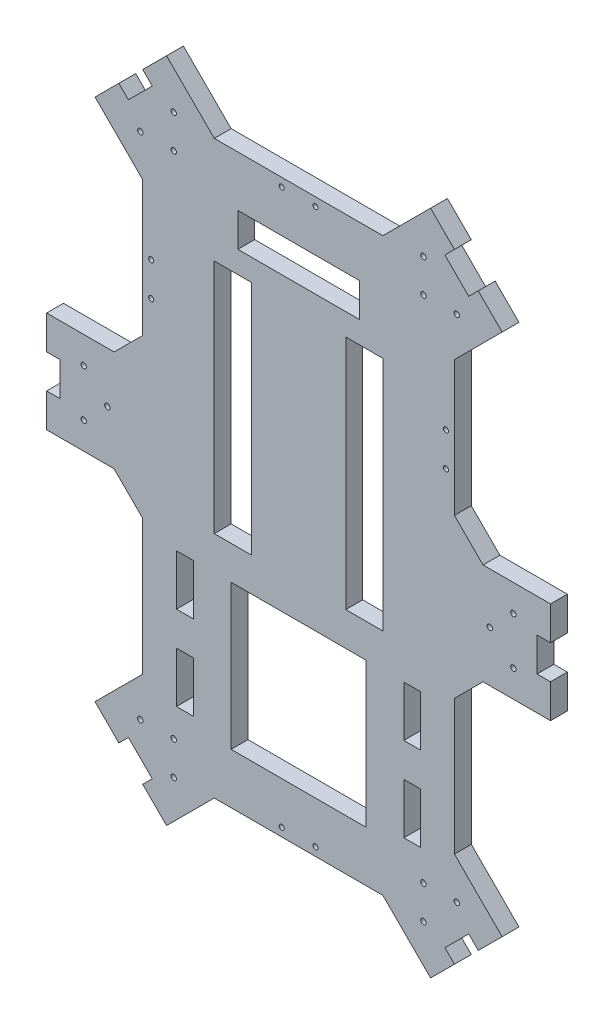
SolidWorks part; units mm, degrees
ref_plane "Płaszczyzna przednia" through (0, 0, 0) normal (0, 0, 1) x (1, 0, 0)
ref_plane "Płaszczyzna górna" through (0, 0, 0) normal (0, 1, 0) x (1, 0, 0)
ref_plane "Płaszczyzna prawa" through (0, 0, 0) normal (1, 0, 0) x (0, 0, -1)
sketch "Szkic1" plane through (0, 0, 0) normal (0, 0, 1) x (1, 0, 0)
  line L0 (0, 0) -> (-50, 0)
  line L1 (-50, 0) -> (-64.1421, 14.1421)
  line L2 (-64.1421, 14.1421) -> (-71.2132, 7.0711)
  line L3 (-71.2132, 7.0711) -> (-68.3848, 4.2426)
  line L4 (-68.3848, 4.2426) -> (-75.4558, -2.8284)
  line L5 (-75.4558, -2.8284) -> (-78.2843, 0)
  line L6 (-78.2843, 0) -> (-85.3553, -7.0711)
  line L7 (-85.3553, -7.0711) -> (-71.2132, -21.2132)
  line L8 (-71.2132, -21.2132) -> (-71.2132, -61.2132)
  line L9 (0, 0) -> (14.1421, 14.1421)
  line L10 (14.1421, 14.1421) -> (21.2132, 7.0711)
  line L11 (21.2132, 7.0711) -> (18.3848, 4.2426)
  line L12 (18.3848, 4.2426) -> (25.4558, -2.8284)
  line L13 (25.4558, -2.8284) -> (28.2843, 0)
  line L14 (28.2843, 0) -> (35.3553, -7.0711)
  line L15 (35.3553, -7.0711) -> (21.2132, -21.2132)
  line L16 (21.2132, -21.2132) -> (21.2132, -61.2132)
  line L17 (-71.2132, -61.2132) -> (-79.6985, -69.6985)
  line L18 (-79.6985, -69.6985) -> (-99.6985, -69.6985)
  line L19 (-99.6985, -69.6985) -> (-99.6985, -79.6985)
  line L20 (-99.6985, -79.6985) -> (-95.6985, -79.6985)
  line L21 (-95.6985, -79.6985) -> (-95.6985, -89.6985)
  line L22 (-95.6985, -89.6985) -> (-99.6985, -89.6985)
  line L23 (-99.6985, -89.6985) -> (-99.6985, -99.6985)
  line L24 (-99.6985, -99.6985) -> (-79.6985, -99.6985)
  line L25 (21.2132, -61.2132) -> (29.6985, -69.6985)
  line L26 (29.6985, -69.6985) -> (49.6985, -69.6985)
  line L27 (49.6985, -69.6985) -> (49.6985, -79.6985)
  line L28 (49.6985, -79.6985) -> (45.6985, -79.6985)
  line L29 (45.6985, -79.6985) -> (45.6985, -89.6985)
  line L30 (45.6985, -89.6985) -> (49.6985, -89.6985)
  line L31 (49.6985, -89.6985) -> (49.6985, -99.6985)
  line L32 (49.6985, -99.6985) -> (29.6985, -99.6985)
  line L33 (29.6985, -99.6985) -> (21.2132, -108.1838)
  line L34 (-79.6985, -99.6985) -> (-71.2132, -108.1838)
  line L35 (-71.2132, -108.1838) -> (-71.2132, -148.1838)
  line L36 (21.2132, -108.1838) -> (21.2132, -148.1838)
  line L37 (-71.2132, -148.1838) -> (-85.3553, -162.3259)
  line L38 (-85.3553, -162.3259) -> (-78.2843, -169.397)
  line L39 (-78.2843, -169.397) -> (-75.4558, -166.5685)
  line L40 (-75.4558, -166.5685) -> (-68.3848, -173.6396)
  line L41 (-68.3848, -173.6396) -> (-71.2132, -176.468)
  line L42 (-71.2132, -176.468) -> (-64.1421, -183.5391)
  line L43 (-64.1421, -183.5391) -> (-50, -169.397)
  line L44 (21.2132, -148.1838) -> (35.3553, -162.3259)
  line L45 (35.3553, -162.3259) -> (28.2843, -169.397)
  line L46 (28.2843, -169.397) -> (25.4558, -166.5685)
  line L47 (25.4558, -166.5685) -> (18.3848, -173.6396)
  line L48 (18.3848, -173.6396) -> (21.2132, -176.468)
  line L49 (21.2132, -176.468) -> (14.1421, -183.5391)
  line L50 (14.1421, -183.5391) -> (0, -169.397)
  line L51 (-50, -169.397) -> (0, -169.397)
  dimension "D1" = 225
  dimension "D2" = 225
  dimension "D3" = 20
  dimension "D4" = 20
  dimension "D5" = 10
  dimension "D6" = 4
  dimension "D7" = 50
  dimension "D8" = 10
  dimension "D9" = 10
  dimension "D10" = 20
  dimension "D11" = 4
  dimension "D12" = 10
  dimension "D13" = 4
  dimension "D14" = 10
  dimension "D15" = 4
  dimension "D16" = 10
  dimension "D17" = 20
  dimension "D18" = 225
  dimension "D19" = 40
  dimension "D20" = 12
  dimension "D21" = 20
  dimension "D22" = 10
  dimension "D23" = 4
  dimension "D24" = 10
  dimension "D25" = 4
  dimension "D26" = 10
  dimension "D27" = 20
  dimension "D29" = 12
  dimension "D30" = 20
  dimension "D31" = 10
  dimension "D32" = 4
  dimension "D33" = 10
  dimension "D34" = 4
  dimension "D35" = 10
  dimension "D36" = 20
  dimension "D37" = 12
  dimension "D38" = 12
  dimension "D39" = 40
  dimension "D40" = 40
  dimension "D41" = 20
  dimension "D42" = 10
  dimension "D43" = 4
  dimension "D44" = 10
  dimension "D45" = 4
  dimension "D46" = 10
  dimension "D47" = 20
  dimension "D48" = 20
  dimension "D49" = 10
  dimension "D50" = 4
  dimension "D51" = 10
  dimension "D52" = 4
  dimension "D53" = 10
  dimension "D54" = 20
  dimension "D55" = 135
  dimension "D56" = 90
  dimension "D57" = 270
  dimension "D58" = 225
  dimension "D59" = 225
  dimension "D60" = 135
extrude "Dodanie-wyciągnięcie1" add sketch "Szkic1" along normal blind 5 contours L36 L44 L45 L46 L47 L48 L49 L50 L51 L43 L42 L41 L40 L39 L38 L37 L35 L34 L24 L23 L22 L21 L20 L19 L18 L17 L8 L7 L6 L5 L4 L3 L2 L1 L0 L9 L10 L11 L12 L13 L14 L15 L16 L25 L26 L27 L28 L29 L30 L31 L32 L33
sketch "Szkic11" plane through (0, 0, 5) normal (0, 0, 1) x (1, 0, 0)
  line L0 (-79.6985, -69.6985) -> (-99.6985, -69.6985) construction
  line L1 (-85.3553, -7.0711) -> (-71.2132, -21.2132) construction
  line L2 (-99.6985, -69.6985) -> (-99.6985, -79.6985) construction
  line L3 (-99.6985, -99.6985) -> (-79.6985, -99.6985) construction
  line L4 (-78.2843, 0) -> (-85.3553, -7.0711) construction
  line L5 (-50, 0) -> (-64.1421, 14.1421) construction
  line L6 (-64.1421, 14.1421) -> (-71.2132, 7.0711) construction
  line L7 (14.1421, 14.1421) -> (21.2132, 7.0711) construction
  line L8 (35.3553, -7.0711) -> (21.2132, -21.2132) construction
  line L9 (28.2843, 0) -> (35.3553, -7.0711) construction
  line L10 (0, 0) -> (14.1421, 14.1421) construction
  line L11 (49.6985, -89.6985) -> (49.6985, -99.6985) construction
  line L12 (49.6985, -99.6985) -> (29.6985, -99.6985) construction
  line L13 (49.6985, -69.6985) -> (49.6985, -79.6985) construction
  line L14 (29.6985, -69.6985) -> (49.6985, -69.6985) construction
  line L15 (21.2132, -176.468) -> (14.1421, -183.5391) construction
  line L16 (14.1421, -183.5391) -> (0, -169.397) construction
  line L17 (35.3553, -162.3259) -> (28.2843, -169.397) construction
  line L18 (21.2132, -148.1838) -> (35.3553, -162.3259) construction
  line L19 (-85.3553, -162.3259) -> (-78.2843, -169.397) construction
  line L20 (-71.2132, -176.468) -> (-64.1421, -183.5391) construction
  line L21 (-64.1421, -183.5391) -> (-50, -169.397) construction
  line L22 (-71.2132, -148.1838) -> (-85.3553, -162.3259) construction
  line L23 (-99.6985, -89.6985) -> (-99.6985, -99.6985) construction
  circle A0 centre (-81.6985, -84.6985) radius 0.8
  circle A1 centre (-88.6985, -77.6985) radius 0.8
  circle A2 centre (-88.6985, -91.6985) radius 0.8
  circle A3 centre (-62.0208, -9.1924) radius 0.8
  circle A4 centre (-62.0208, 0.7071) radius 0.8
  circle A5 centre (-71.9203, -9.1924) radius 0.8
  circle A6 centre (12.0208, -9.1924) radius 0.8
  circle A7 centre (12.0208, 0.7071) radius 0.8
  circle A8 centre (21.9203, -9.1924) radius 0.8
  circle A9 centre (31.6985, -84.6985) radius 0.8
  circle A10 centre (38.6985, -77.6985) radius 0.8
  circle A11 centre (38.6985, -91.6985) radius 0.8
  circle A12 centre (12.0208, -160.2046) radius 0.8
  circle A13 centre (21.9203, -160.2046) radius 0.8
  circle A14 centre (12.0208, -170.1041) radius 0.8
  circle A15 centre (-62.0208, -160.2046) radius 0.8
  circle A16 centre (-71.9203, -160.2046) radius 0.8
  circle A17 centre (-62.0208, -170.1041) radius 0.8
  dimension "D1" = 1.6
  dimension "D4" = 1.6
  dimension "D5" = 1.6
  dimension "D10" = 1.6
  dimension "D11" = 1.6
  dimension "D12" = 1.6
  dimension "D19" = 1.6
  dimension "D20" = 1.6
  dimension "D21" = 1.6
  dimension "D30" = 1.6
  dimension "D31" = 1.6
  dimension "D32" = 1.6
  dimension "D41" = 1.6
  dimension "D42" = 1.6
  dimension "D43" = 1.6
  dimension "D50" = 1.6
  dimension "D51" = 1.6
  dimension "D52" = 1.6
  dimension "D2" = 15
  dimension "D3" = 18
  dimension "D6" = 7
  dimension "D7" = 7
  dimension "D8" = 8
  dimension "D9" = 8
  dimension "D13" = 18
  dimension "D14" = 15
  dimension "D15" = 8
  dimension "D16" = 8
  dimension "D17" = 11
  dimension "D18" = 11
  dimension "D22" = 18
  dimension "D23" = 15
  dimension "D24" = 11
  dimension "D25" = 11
  dimension "D26" = 8
  dimension "D27" = 8
  dimension "D28" = 14
  dimension "D29" = 14
  dimension "D33" = 18
  dimension "D34" = 15
  dimension "D35" = 11
  dimension "D36" = 11
  dimension "D37" = 8
  dimension "D38" = 8
  dimension "D39" = 14
  dimension "D40" = 7
  dimension "D44" = 18
  dimension "D45" = 15
  dimension "D46" = 11
  dimension "D47" = 11
  dimension "D48" = 8
  dimension "D49" = 8
  dimension "D53" = 18
  dimension "D54" = 11
  dimension "D55" = 11
  dimension "D56" = 8
  dimension "D57" = 15
  dimension "D58" = 8
  dimension "D59" = 14
  dimension "D60" = 14
  dimension "D61" = 14
  dimension "D62" = 11
  dimension "D63" = 11
extrude "Wytnij-wyciągnięcie7" cut sketch "Szkic11" against normal blind 60 and the other way blind 42
sketch "Szkic12" plane through (0, 0, 5) normal (0, 0, 1) x (1, 0, 0)
  line L0 (0, 0) -> (-50, 0) construction
  line L1 (-71.2132, -21.2132) -> (-71.2132, -61.2132) construction
  line L2 (-50, -169.397) -> (0, -169.397) construction
  line L3 (21.2132, -21.2132) -> (21.2132, -61.2132) construction
  circle A0 centre (-30, -2.5) radius 0.75
  circle A1 centre (-20, -2.5) radius 0.75
  circle A2 centre (-30, -166.897) radius 0.75
  circle A3 centre (-20, -166.897) radius 0.75
  circle A4 centre (-68.7132, -40.5) radius 0.75
  circle A5 centre (-68.7132, -50.5) radius 0.75
  circle A6 centre (18.7132, -40.5) radius 0.75
  circle A7 centre (18.7132, -50.5) radius 0.75
  dimension "D2" = 1.5
  dimension "D3" = 1.5
  dimension "D8" = 1.5
  dimension "D9" = 1.5
  dimension "D15" = 1.5
  dimension "D16" = 1.5
  dimension "D17" = 1.5
  dimension "D18" = 1.5
  dimension "D1" = 2.5
  dimension "D4" = 2.5
  dimension "D5" = 20
  dimension "D6" = 10
  dimension "D7" = 20
  dimension "D10" = 2.5
  dimension "D11" = 2.5
  dimension "D12" = 20
  dimension "D13" = 10
  dimension "D14" = 20
  dimension "D19" = 2.5
  dimension "D20" = 2.5
  dimension "D21" = 2.5
  dimension "D22" = 2.5
  dimension "D23" = 40.5
  dimension "D24" = 50.5
  dimension "D25" = 40.5
  dimension "D26" = 50.5
extrude "Wytnij-wyciągnięcie8" cut sketch "Szkic12" against normal blind 66 and the other way blind 36
sketch "Szkic13" plane through (0, 0, 0) normal (0, 0, 1) x (1, 0, 0)
  line L0 (0, 0) -> (-50, 0) construction
  line L1 (-50.0032, -31.5) -> (-39.0032, -31.5)
  line L2 (-50.0032, -31.5) -> (-50.0032, -101.5)
  line L3 (-50.0032, -101.5) -> (-39.0032, -101.5)
  line L4 (-39.0032, -31.5) -> (-39.0032, -101.5)
  line L5 (0.0032, -31.5) -> (-10.9968, -31.5)
  line L6 (0.0032, -31.5) -> (0.0032, -101.5)
  line L7 (0.0032, -101.5) -> (-10.9968, -101.5)
  line L8 (-10.9968, -31.5) -> (-10.9968, -101.5)
  line L9 (-71.2132, -21.2132) -> (-71.2132, -61.2132) construction
  line L10 (21.2132, -21.2132) -> (21.2132, -61.2132) construction
  line L11 (-71.2132, -108.1838) -> (-71.2132, -148.1838) construction
  line L12 (-45.0032, -111.497) -> (-5.0032, -111.497)
  line L13 (-45.0032, -111.497) -> (-45.0032, -154.397)
  line L14 (-45.0032, -154.397) -> (-5.0032, -154.397)
  line L15 (-5.0032, -111.497) -> (-5.0032, -154.397)
  line L16 (21.2132, -108.1838) -> (21.2132, -148.1838) construction
  line L17 (-50, -169.397) -> (0, -169.397) construction
  line L19 (-61.2132, -111.497) -> (-56.2132, -111.497)
  line L20 (-61.2132, -111.497) -> (-61.2132, -126.497)
  line L21 (-61.2132, -126.497) -> (-56.2132, -126.497)
  line L22 (-56.2132, -111.497) -> (-56.2132, -126.497)
  line L23 (-61.2132, -136.497) -> (-56.2132, -136.497)
  line L24 (-61.2132, -136.497) -> (-61.2132, -151.497)
  line L25 (-61.2132, -151.497) -> (-56.2132, -151.497)
  line L26 (-56.2132, -136.497) -> (-56.2132, -151.497)
  line L27 (6.2132, -111.5) -> (11.2132, -111.5)
  line L28 (6.2132, -111.5) -> (6.2132, -126.5)
  line L29 (6.2132, -126.5) -> (11.2132, -126.5)
  line L30 (11.2132, -111.5) -> (11.2132, -126.5)
  line L31 (6.2132, -136.5) -> (11.2132, -136.5)
  line L32 (6.2132, -136.5) -> (6.2132, -151.5)
  line L33 (6.2132, -151.5) -> (11.2132, -151.5)
  line L34 (11.2132, -136.5) -> (11.2132, -151.5)
  line L35 (-43.0032, -15) -> (-7.0032, -15)
  line L36 (-43.0032, -15) -> (-43.0032, -25)
  line L37 (-43.0032, -25) -> (-7.0032, -25)
  line L38 (-7.0032, -15) -> (-7.0032, -25)
  dimension "D1" = 70
  dimension "D2" = 31.5
  dimension "D3" = 21.21
  dimension "D4" = 11
  dimension "D5" = 11
  dimension "D6" = 31.5
  dimension "D7" = 70
  dimension "D8" = 21.21
  dimension "D9" = 40
  dimension "D10" = 26.21
  dimension "D11" = 26.2164
  dimension "D12" = 42.9
  dimension "D13" = 15
  dimension "D14" = 9.997
  dimension "D15" = 10
  dimension "D16" = 5
  dimension "D17" = 9.997
  dimension "D18" = 15
  dimension "D19" = 10
  dimension "D20" = 5
  dimension "D21" = 10
  dimension "D22" = 15
  dimension "D23" = 5
  dimension "D24" = 5
  dimension "D25" = 10
  dimension "D26" = 15
  dimension "D27" = 10
  dimension "D28" = 10
  dimension "D29" = 15
  dimension "D30" = 10
  dimension "D31" = 11.2164
  dimension "D32" = 28.21
  dimension "D33" = 36
  dimension "D34" = 28.2164
  dimension "D35" = 10
  dimension "D36" = 15
extrude "Wytnij-wyciągnięcie9" cut sketch "Szkic13" against normal blind 47 and the other way blind 54
